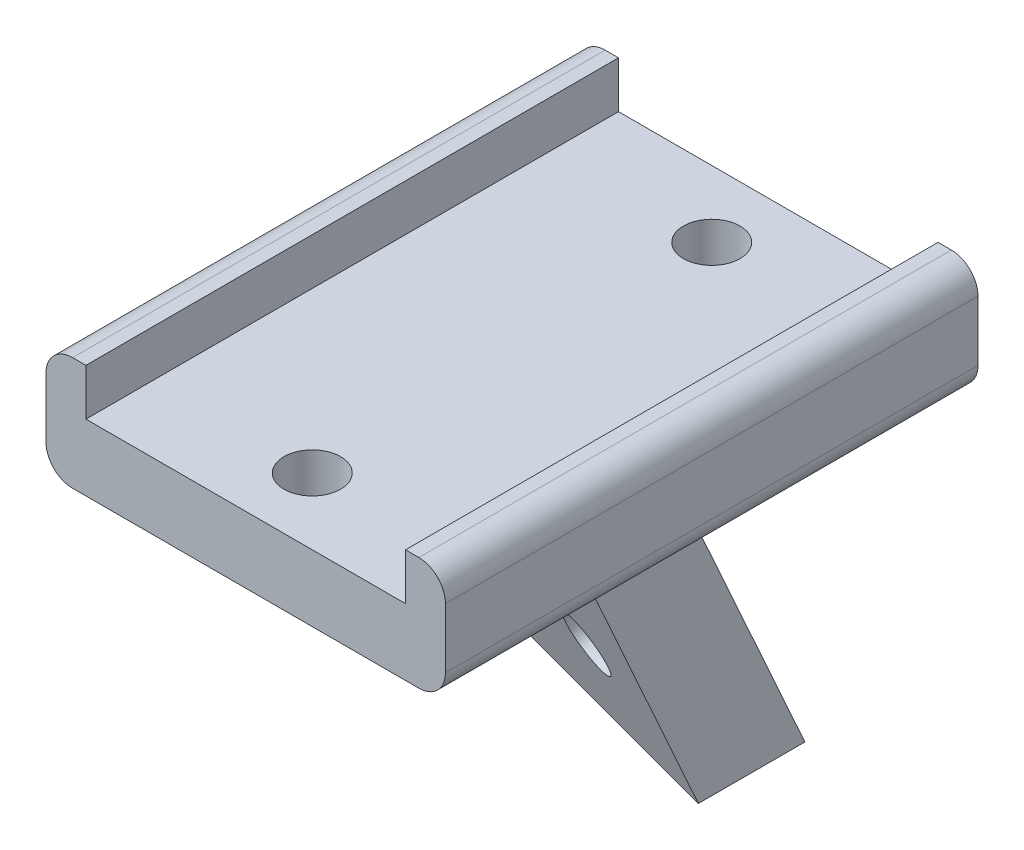
SolidWorks part; units mm, degrees
ref_plane "Front Plane" through (0, 0, 0) normal (0, 0, 1) x (1, 0, 0)
ref_plane "Top Plane" through (0, 0, 0) normal (0, 1, 0) x (1, 0, 0)
ref_plane "Right Plane" through (0, 0, 0) normal (1, 0, 0) x (0, 0, -1)
sketch "Sketch1" plane through (0, 0, 0) normal (0, 1, 0) x (1, 0, 0)
  line L1 (-11, -20) -> (11, -20)
  line L2 (-11, -20) -> (-11, 20)
  line L3 (-11, 20) -> (11, 20)
  line L4 (11, -20) -> (11, 20)
  line L5 (-11, -20) -> (11, 20) construction
  line L6 (-11, 20) -> (11, -20) construction
  circle A0 centre (0, 15) radius 2.125
  circle A1 centre (0, -15) radius 2.125
  point P0 (0, 0)
  dimension "D3" = 30
  dimension "D4" = 15
  dimension "D5" = 4.25
  dimension "D6" = 4.25
  dimension "D1" = 22
  dimension "D2" = 40
extrude "Boss-Extrude1" add sketch "Sketch1" along normal blind 5
sketch "Sketch2" plane through (0, 0, 0) normal (0, -1, 0) x (1, 0, 0)
  line L0 (-11, 0.1051) -> (11, 6)
  line L1 (-11, -20) -> (-11, 20) construction
  line L2 (11, 20) -> (11, -20) construction
  line L3 (11, 6) -> (11, -2)
  line L4 (11, -2) -> (-11, -7.8949)
  line L5 (-11, -7.8949) -> (-11, 0.1051)
  dimension "D1" = 8
  dimension "D2" = 14
  dimension "D3" = 105
sketch "Sketch4" plane through (0, 0, -20) normal (0, 0, -1) x (-1, 0, 0)
  line L0 (-11, 5) -> (-12, 5)
  line L1 (-12, 5) -> (-12, 8.5)
  line L2 (-12, 8.5) -> (-15, 8.5)
  line L3 (-15, 8.5) -> (-15, 0)
  line L4 (-15, 0) -> (-11, 0)
  line L5 (-11, 0) -> (-11, 5)
  line L6 (0, 0) -> (0, 5) construction
  line L7 (-11, 0) -> (11, 0) construction
  line L8 (-11, 5) -> (11, 5) construction
  line L9 (11, 0) -> (11, 5)
  line L10 (15, 0) -> (11, 0)
  line L11 (15, 8.5) -> (15, 0)
  line L12 (12, 8.5) -> (15, 8.5)
  line L13 (12, 5) -> (12, 8.5)
  line L14 (11, 5) -> (12, 5)
  dimension "D1" = 1
  dimension "D2" = 3.5
  dimension "D3" = 3
extrude "Boss-Extrude3" add sketch "Sketch4" against normal up to surface (40 mm away) up to face at (0, 2.5, 20)
fillet "Fillet1" radius 2 4 edges at (15, 0, 0) (-15, 0, 0) (-15, 8.5, 0) (15, 8.5, 0)
ref_plane "Plane1" through (0, -20, 0) normal (0, -1, 0) x (-1, 0, 0)
sketch "Sketch5" plane through (0, -20, 0) normal (0, -1, 0) x (-1, 0, 0)
  line L0 (-11, 3) -> (-11, 11)
  line L1 (-11, 11) -> (11, 16.8949)
  line L2 (11, 16.8949) -> (11, 8.8949)
  line L3 (11, 8.8949) -> (-11, 3)
  line L4 (-13, 20) -> (-13, -20) construction
  line L5 (13, -20) -> (13, 20) construction
  line L6 (13, -20) -> (-13, -20) construction
  dimension "D1" = 8
  dimension "D2" = 2
  dimension "D3" = 2
  dimension "D4" = 105
  dimension "D5" = 23
loft "Loft1" add profiles "Sketch2", "Sketch5" connector at (11, 0, -2) connector at (11, -20, -11)
ref_plane "Plane2" through (1.0403, 1.7471, -3.8825) normal (-0.2374, -0.3986, 0.8859) x (0.9714, -0.0974, 0.2165)
sketch "Sketch6" plane through (1.0403, 1.7471, -3.8825) normal (-0.2374, -0.3986, 0.8859) x (0.9714, -0.0974, 0.2165)
  line L0 (10.2527, -0.8207) -> (10.2527, -22.7524) construction
  line L1 (-12.3945, -3.2398) -> (-12.3945, -25.1715) construction
  line L2 (-12.3945, -3.2398) -> (10.2527, -0.8207) construction
  circle A0 centre (5.2527, -11.4117) radius 2.125
  circle A1 centre (-7.3945, -12.7626) radius 2.125
  point P6 (10.2527, -11.7866)
  dimension "D1" = 4.25
  dimension "D2" = 4.25
  dimension "D3" = 5
  dimension "D4" = 5
  dimension "D5" = 10
  dimension "D6" = 10
extrude "Cut-Extrude1" cut sketch "Sketch6" along normal up to surface (7.0869 mm away) up to face at (5.5, -5, 2.2763)
